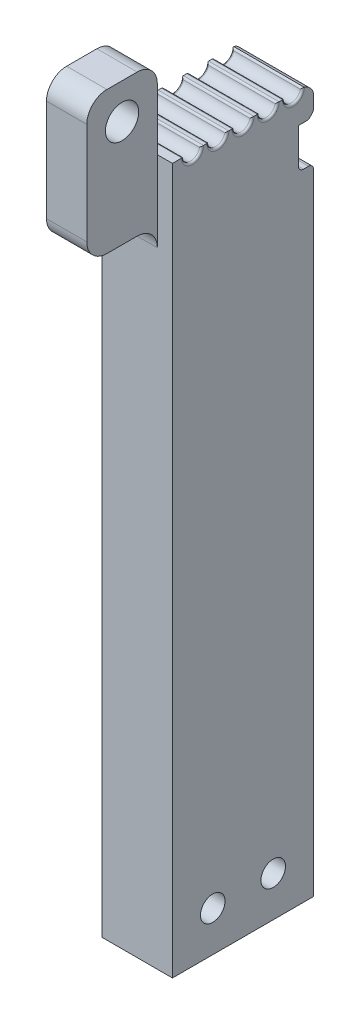
SolidWorks part; units mm, degrees
ref_plane "Front Plane" through (0, 0, 0) normal (0, 0, 1) x (1, 0, 0)
ref_plane "Top Plane" through (0, 0, 0) normal (0, 1, 0) x (1, 0, 0)
ref_plane "Right Plane" through (0, 0, 0) normal (1, 0, 0) x (0, 0, -1)
sketch "Sketch1" plane through (0, 0, 0) normal (0, 1, 0) x (1, 0, 0)
  line L1 (-3.5, 7) -> (3.5, 7)
  line L2 (-3.5, 7) -> (-3.5, -7)
  line L3 (-3.5, -7) -> (3.5, -7)
  line L4 (3.5, 7) -> (3.5, -7)
  line L5 (-3.5, 7) -> (3.5, -7) construction
  line L6 (-3.5, -7) -> (3.5, 7) construction
  point P0 (0, 0)
  dimension "D1" = 14
  dimension "D2" = 7
extrude "Boss-Extrude1" add sketch "Sketch1" along normal blind 70
hole_wizard "CBORE for #2 Socket Head Cap Screw1" positions "Sketch2" profile "Sketch3" counterbore size "#2" standard "ANSI Inch" end condition up to next
sketch "Sketch2" plane through (-3.5, 0, 0) normal (1, 0, 0) x (0, 0, -1)
  line L0 (-9.0555, 4) -> (8.8936, 4) construction
  line L2 (0, 6.5633) -> (0, -1.0659) construction
  line L4 (3.8722, 0) -> (-3.8722, 0) construction
  point P0 (-3, 4)
  point P16 (3, 4)
  dimension "D1" = 4
  dimension "D2" = 6
sketch "Sketch3" plane through (-3.5, 4, 3) normal (0, 1, 0) x (0, 0, 1)
  line L0 (0, 0) -> (0, 7)
  line L1 (0, 7) -> (1.2192, 7)
  line L3 (1.2192, 7) -> (1.2192, 2.1844)
  line L4 (1.2192, 2.1844) -> (2.3812, 2.1844)
  line L5 (2.3812, 2.1844) -> (2.3812, 0)
  line L7 (2.3812, 0) -> (0, 0)
  line L11 (0, -6.35) -> (0, 107.95) construction
  dimension "Thru Hole Dia." = 2.4384
  dimension "Thru Hole Depth" = 7
  dimension "C'Bore Dia." = 4.7625
  dimension "C'Bore Depth" = 2.1844
sketch "Sketch4" plane through (3.5, 0, 0) normal (1, 0, 0) x (0, 0, -1)
  line L0 (0, 3.8722) -> (0, -3.8722) construction
  line L1 (-7, 70) -> (7, 70) construction
  arc A0 (0.9, 70) -> (-0.9, 70) centre (0, 70) cw
  dimension "D1" = 0.9
extrude "Cut-Extrude2" cut sketch "Sketch4" against normal through all flip side to cut
pattern_linear "LPattern1" count 3 spacing 2.5 along (0, 0, 1) count 3 spacing 2.5 along (0, 0, -1) of "Cut-Extrude2"
fillet "Fillet1" radius 0.2 20 edges at (-3.5, 69.1, 0) (3.5, 69.1, 0) (-3.5, 69.1, -5) (-3.5, 69.1, -2.5) (-3.5, 69.1, 2.5) (-3.5, 69.1, 5) (3.5, 69.1, -5) (3.5, 69.1, -2.5) (3.5, 69.1, 5) (3.5, 69.1, 2.5) (0, 70, -4.1) (0, 70, -5.9) (0, 70, -1.6) (0, 70, -3.4) (0, 70, 0.9) (0, 70, -0.9) (0, 70, 3.4) (0, 70, 1.6) (0, 70, 5.9) (0, 70, 4.1)
chamfer "Chamfer1" distance 0.7 angle 45 1 edges at (0, 70, -7)
fillet "Fillet2" radius 1 2 edges at (0, 69.3, -7) (0, 70, -6.3)
sketch "Sketch6" plane through (0, 0, 0) normal (1, 0, 0) x (0, 0, -1)
  line L0 (7, 68.8858) -> (7, 0) construction
  line L2 (7, 67) -> (5.5, 67)
  line L3 (7, 67) -> (7, 63)
  line L4 (7, 63) -> (5.5, 63)
  line L5 (5.5, 67) -> (5.5, 63)
  line L6 (6.1, 70) -> (6.3, 70) construction
  dimension "D1" = 1.5
  dimension "D2" = 4
  dimension "D3" = 3
extrude "Cut-Extrude4" cut sketch "Sketch6" against normal through all both and the other way through all
chamfer "Chamfer2" distance 0.5 angle 45 1 edges at (0, 67, -7)
fillet "Fillet4" radius 0.5 4 edges at (0, 67, -6.5) (0, 67.5, -7) (0, 63, -5.5) (0, 63, -7)
sketch "Sketch7" plane through (0, 0, 0) normal (1, 0, 0) x (0, 0, -1)
  line L0 (-7, 70) -> (-7, 0) construction
  line L1 (-7, 64) -> (-14, 64)
  line L2 (-7, 64) -> (-7, 78.1)
  line L3 (-7, 78.1) -> (-14, 78.1)
  line L4 (-14, 64) -> (-14, 78.1)
  line L5 (-7, 70) -> (-6.1, 70) construction
  dimension "D1" = 7
  dimension "D2" = 8.1
  dimension "D3" = 6
extrude "Boss-Extrude2" add sketch "Sketch7" against normal mid plane 4
sketch "Sketch9" plane through (2, 0, 0) normal (1, 0, 0) x (0, 0, -1)
  line L0 (-10.5, 123.815) -> (-10.5, 25.385) construction
  line L1 (-7, 78.1) -> (-14, 78.1) construction
  circle A0 centre (-10.5, 74.6) radius 1.65
  point P4 (-10.5, 78.1)
  point P7 (-10.5, 74.6)
  dimension "D1" = 3.3
  dimension "D2" = 3.5
extrude "Cut-Extrude5" cut sketch "Sketch9" against normal up to next
fillet "Fillet5" radius 2 4 edges at (0, 64, 14) (0, 64, 7) (0, 78.1, 7) (0, 78.1, 14)
